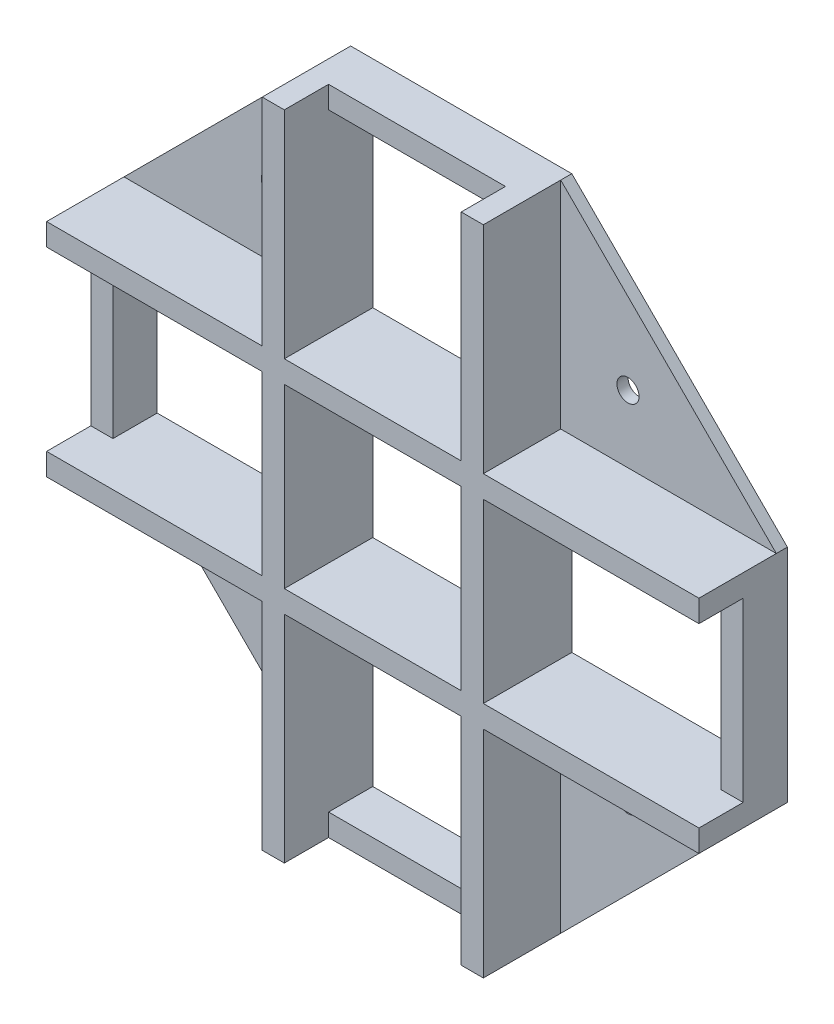
SolidWorks part; units mm, degrees
ref_plane "Front Plane" through (0, 0, 0) normal (0, 0, 1) x (1, 0, 0)
ref_plane "Top Plane" through (0, 0, 0) normal (0, 1, 0) x (1, 0, 0)
ref_plane "Right Plane" through (0, 0, 0) normal (1, 0, 0) x (0, 0, -1)
sketch "Sketch1" plane through (0, 0, 0) normal (0, 0, 1) x (1, 0, 0)
  line L1 (12.7, -37.465) -> (-12.7, -37.465)
  line L2 (12.7, -37.465) -> (12.7, 37.465)
  line L3 (12.7, 37.465) -> (-12.7, 37.465)
  line L4 (-12.7, -37.465) -> (-12.7, 37.465)
  line L5 (12.7, -37.465) -> (-12.7, 37.465) construction
  line L6 (12.7, 37.465) -> (-12.7, -37.465) construction
  line L7 (37.465, -12.7) -> (-37.465, -12.7)
  line L8 (37.465, -12.7) -> (37.465, 12.7)
  line L9 (37.465, 12.7) -> (-37.465, 12.7)
  line L10 (-37.465, -12.7) -> (-37.465, 12.7)
  line L11 (37.465, -12.7) -> (-37.465, 12.7) construction
  line L12 (37.465, 12.7) -> (-37.465, -12.7) construction
  point P0 (0, 0)
  point P6 (0, 0)
  dimension "D1" = 74.93
  dimension "D2" = 25.4
  dimension "D3" = 25.4
  dimension "D4" = 74.93
extrude "Boss-Extrude1" add sketch "Sketch1" along normal blind 10.16 contours L10 L7 L4 L9 | L2 L9 L4 L7 | L9 L2 L3 L4 | L8 L9 L2 L7 | L2 L7 L4 L1 region at (0, -25.0825, 0) region at (0, 0, 0) region at (25.0825, 0, 0) region at (-25.0825, 0, 0) region at (0, 25.0825, 0)
sketch "Sketch2" plane through (0, 0, 10.16) normal (0, 0, 1) x (1, 0, 0)
  line L0 (0, 0) -> (0, 16.4382) construction
  line L1 (10.16, -10.16) -> (-10.16, -10.16)
  line L2 (10.16, -10.16) -> (10.16, 10.16)
  line L3 (10.16, 10.16) -> (-10.16, 10.16)
  line L4 (-10.16, -10.16) -> (-10.16, 10.16)
  line L5 (10.16, -10.16) -> (-10.16, 10.16) construction
  line L6 (10.16, 10.16) -> (-10.16, -10.16) construction
  line L7 (10.16, 12.7) -> (-10.16, 12.7)
  line L8 (10.16, 12.7) -> (10.16, 34.925)
  line L9 (10.16, 34.925) -> (-10.16, 34.925)
  line L10 (-10.16, 12.7) -> (-10.16, 34.925)
  line L11 (10.16, 12.7) -> (-10.16, 34.925) construction
  line L12 (10.16, 34.925) -> (-10.16, 12.7) construction
  line L13 (0, 0) -> (-32.0898, 0) construction
  line L14 (10.16, -34.925) -> (-10.16, -34.925)
  line L15 (-10.16, -12.7) -> (-10.16, -34.925)
  line L16 (10.16, -12.7) -> (-10.16, -12.7)
  line L17 (10.16, -12.7) -> (10.16, -34.925)
  line L18 (-34.925, 10.16) -> (-12.7, 10.16)
  line L19 (34.925, -10.16) -> (12.7, -10.16)
  line L20 (34.925, -10.16) -> (34.925, 10.16)
  line L21 (34.925, 10.16) -> (12.7, 10.16)
  line L22 (12.7, -10.16) -> (12.7, 10.16)
  line L23 (34.925, -10.16) -> (12.7, 10.16) construction
  line L24 (34.925, 10.16) -> (12.7, -10.16) construction
  line L25 (-12.7, -10.16) -> (-12.7, 10.16)
  line L26 (-34.925, -10.16) -> (-12.7, -10.16)
  line L27 (-34.925, -10.16) -> (-34.925, 10.16)
  point P0 (0, 0)
  point P6 (0, 23.8125)
  point P20 (23.8125, 0)
  dimension "D1" = 20.32
  dimension "D2" = 20.32
  dimension "D3" = 22.225
  dimension "D4" = 2.54
  dimension "D5" = 20.32
  dimension "D6" = 22.225
  dimension "D7" = 20.32
  dimension "D8" = 2.54
extrude "Cut-Extrude1" cut sketch "Sketch2" against normal blind 10.16
sketch "Sketch4" plane through (0, 0, 10.16) normal (0, 0, 1) x (1, 0, 0)
  line L0 (12.7, 37.465) -> (-12.7, 37.465) construction
  line L1 (10.16, 34.925) -> (-10.16, 34.925)
  line L2 (10.16, 34.925) -> (10.16, 37.465)
  line L3 (10.16, 37.465) -> (-10.16, 37.465)
  line L4 (-10.16, 34.925) -> (-10.16, 37.465)
  line L5 (10.16, 12.7) -> (10.16, 34.925) construction
  line L6 (-10.16, 34.925) -> (-10.16, 12.7) construction
  line L12 (37.465, -12.7) -> (37.465, 12.7) construction
  line L13 (34.925, 10.16) -> (37.465, 10.16)
  line L14 (34.925, 10.16) -> (34.925, -10.16)
  line L15 (34.925, -10.16) -> (37.465, -10.16)
  line L16 (37.465, 10.16) -> (37.465, -10.16)
  line L17 (12.7, -10.16) -> (34.925, -10.16) construction
  line L18 (34.925, 10.16) -> (12.7, 10.16) construction
  line L19 (0, 0) -> (17.8539, 0) construction
  line L20 (0, 0) -> (0, -24.0674) construction
  line L21 (-34.925, -10.16) -> (-37.465, -10.16)
  line L22 (-34.925, 10.16) -> (-37.465, 10.16)
  line L23 (-34.925, 10.16) -> (-34.925, -10.16)
  line L24 (-37.465, 10.16) -> (-37.465, -10.16)
  line L25 (10.16, -37.465) -> (-10.16, -37.465)
  line L26 (-10.16, -34.925) -> (-10.16, -37.465)
  line L27 (10.16, -34.925) -> (-10.16, -34.925)
  line L28 (10.16, -34.925) -> (10.16, -37.465)
extrude "Cut-Extrude2" cut sketch "Sketch4" against normal blind 5.08
sketch "Sketch5" plane through (0, 0, 0) normal (0, 0, 1) x (1, 0, 0)
  line L0 (-37.465, 12.7) -> (-12.7, 37.465)
  line L1 (-12.7, 37.465) -> (-12.7, 12.7)
  line L2 (-12.7, 12.7) -> (-37.465, 12.7)
  line L3 (12.7, 37.465) -> (37.465, 12.7)
  line L4 (37.465, 12.7) -> (12.7, 12.7)
  line L5 (12.7, 12.7) -> (12.7, 37.465)
  line L6 (0, 0) -> (7.2753, 7.2753) construction
  line L7 (0, 0) -> (-12.7, 12.7) construction
  line L8 (37.465, -12.7) -> (12.7, -12.7)
  line L9 (12.7, -37.465) -> (37.465, -12.7)
  line L10 (12.7, -12.7) -> (12.7, -37.465)
  line L11 (-12.7, -37.465) -> (-12.7, -12.7)
  line L12 (-37.465, -12.7) -> (-12.7, -37.465)
  line L13 (-12.7, -12.7) -> (-37.465, -12.7)
extrude "Boss-Extrude2" add sketch "Sketch5" along normal blind 1.27
sketch "Sketch6" plane through (0, 0, 1.27) normal (0, 0, 1) x (1, 0, 0)
  line L0 (0, 0) -> (-10.16, 10.16) construction
  line L1 (0, 0) -> (10.16, 10.16) construction
  circle A0 centre (-20.4251, 20.4251) radius 1.27
  circle A1 centre (20.4251, 20.4251) radius 1.27
  circle A2 centre (20.4251, -20.4251) radius 1.27
  circle A3 centre (-20.4251, -20.4251) radius 1.27
  dimension "D1" = 10.925
  dimension "D2" = 2.54
  dimension "D4" = 2.54
  dimension "D3" = 10.925
extrude "Cut-Extrude3" cut sketch "Sketch6" against normal blind 1.27
sketch "Sketch7" plane through (0, 0, 10.16) normal (0, 0, 1) x (1, 0, 0)
  line L0 (-10.16, 10.16) -> (10.16, -10.16) construction
  line L1 (-10.16, -10.16) -> (10.16, 10.16) construction
  point P8 (0, 0)
